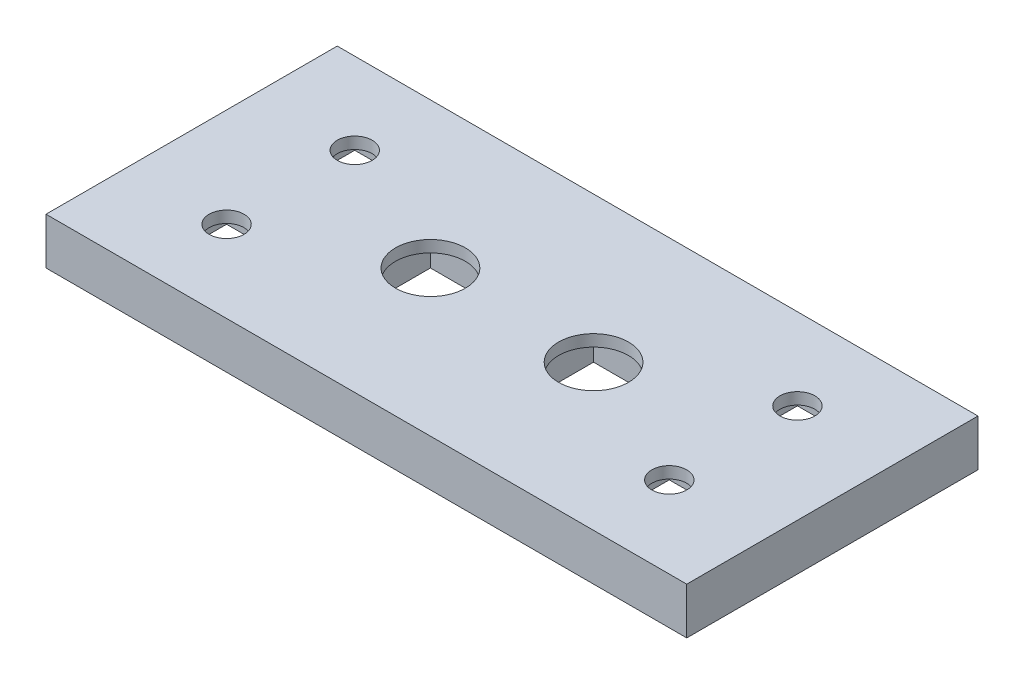
SolidWorks part; units mm, degrees
ref_plane "Front Plane" through (0, 0, 0) normal (0, 0, 1) x (1, 0, 0)
ref_plane "Top Plane" through (0, 0, 0) normal (0, 1, 0) x (1, 0, 0)
ref_plane "Right Plane" through (0, 0, 0) normal (1, 0, 0) x (0, 0, -1)
sketch "Sketch1" plane through (0, 0, 0) normal (0, 1, 0) x (1, 0, 0)
  line L0 (0, 12.5) -> (55, 12.5) construction
  line L1 (0, 0) -> (55, 0)
  line L2 (0, 0) -> (0, 25)
  line L3 (0, 25) -> (55, 25)
  line L4 (55, 0) -> (55, 25)
  line L5 (27.5, 25) -> (27.5, 0) construction
  line L6 (4.5, 3) -> (12.5, 3)
  line L7 (16.5, 8.5) -> (24.5, 8.5)
  line L8 (16.5, 8.5) -> (16.5, 16.5)
  line L9 (16.5, 16.5) -> (24.5, 16.5)
  line L10 (24.5, 8.5) -> (24.5, 16.5)
  line L11 (16.5, 8.5) -> (24.5, 16.5) construction
  line L12 (16.5, 16.5) -> (24.5, 8.5) construction
  line L13 (4.5, 14) -> (12.5, 14)
  line L14 (4.5, 14) -> (4.5, 22)
  line L15 (4.5, 22) -> (12.5, 22)
  line L16 (12.5, 14) -> (12.5, 22)
  line L17 (4.5, 14) -> (12.5, 22) construction
  line L18 (4.5, 22) -> (12.5, 14) construction
  line L19 (12.5, 11) -> (12.5, 3)
  line L20 (4.5, 11) -> (12.5, 11)
  line L21 (4.5, 11) -> (4.5, 3)
  line L22 (38.5, 16.5) -> (30.5, 16.5)
  line L23 (30.5, 8.5) -> (30.5, 16.5)
  line L24 (38.5, 8.5) -> (30.5, 8.5)
  line L25 (38.5, 8.5) -> (38.5, 16.5)
  line L26 (50.5, 11) -> (50.5, 3)
  line L27 (50.5, 11) -> (42.5, 11)
  line L28 (42.5, 11) -> (42.5, 3)
  line L29 (50.5, 3) -> (42.5, 3)
  line L30 (50.5, 14) -> (50.5, 22)
  line L31 (50.5, 22) -> (42.5, 22)
  line L32 (50.5, 14) -> (42.5, 14)
  line L33 (42.5, 14) -> (42.5, 22)
  circle A0 centre (8.5, 18) radius 1.5
  circle A1 centre (20.5, 12.5) radius 3
  circle A2 centre (8.5, 7) radius 1.5
  circle A3 centre (34.5, 12.5) radius 3
  circle A4 centre (46.5, 7) radius 1.5
  circle A5 centre (46.5, 18) radius 1.5
  point P9 (20.5, 12.5)
  point P14 (8.5, 18)
  dimension "D4" = 3
  dimension "D8" = 6
  dimension "D1" = 55
  dimension "D2" = 25
  dimension "D3" = 8
  dimension "D5" = 7
  dimension "D6" = 5.5
  dimension "D7" = 19
extrude "Boss-Extrude1" add sketch "Sketch1" along normal blind 4 contours L1 L4 L3 L2
extrude "Cut-Extrude3" cut sketch "Sketch1<3>" along normal blind 3 contours L29 L26 L27 L28 A4 | L33 L32 L30 L31 A5 | L24 L25 L22 L23 A3 | L20 L21 L6 L19 A2 | L8 L9 L10 L7 | L14 L15 L16 L13 region at (4.6131, 0, -7) region at (38.3869, 0, -12.5) region at (50.3869, 0, -7) region at (46.5, 0, -14.1131)
sketch "Sketch1<3>" plane through (0, 0, 0) normal (0, 1, 0) x (1, 0, 0) same geometry as "Sketch1"
extrude "Cut-Extrude4" cut sketch "Sketch1<4>" along normal through all contours A0 | A5 | A4 | A3 | A1 | A2 region at (8.5, 0, -18)
sketch "Sketch1<4>" plane through (0, 0, 0) normal (0, 1, 0) x (1, 0, 0) same geometry as "Sketch1"
